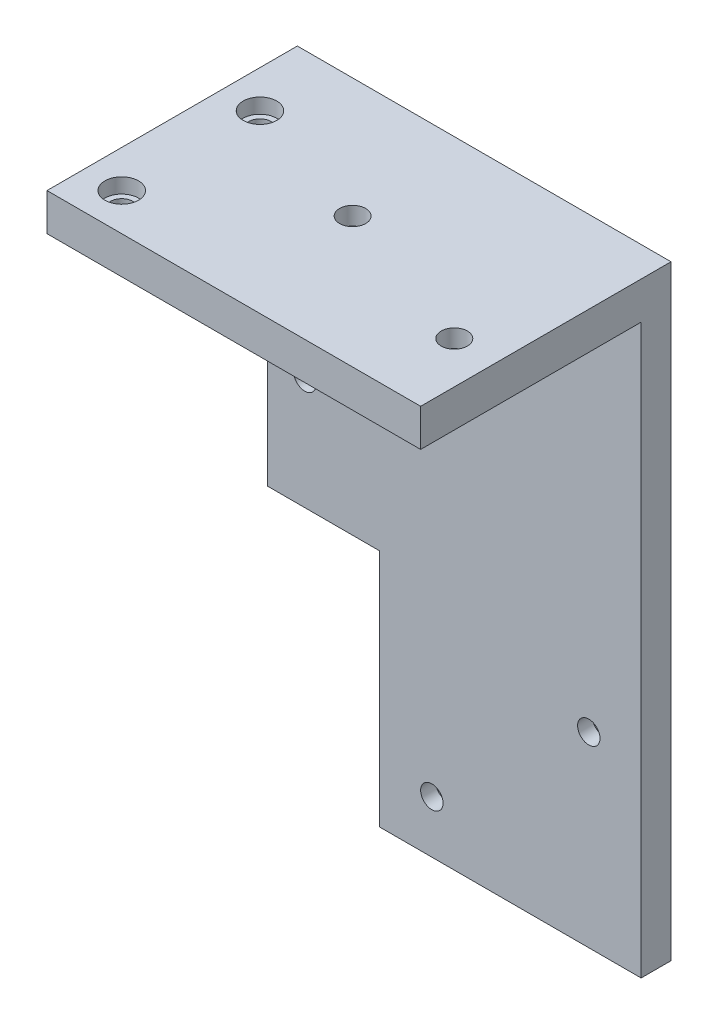
SolidWorks part; units mm, degrees
other "标注1"
sketch "草图3" plane through (0, 5, 29.5) normal (-0.6417, 0.7662, 0.0339) x (0.7661, 0.6384, 0.0747)
ref_plane "前视基准面" through (0, 0, 0) normal (0, 0, 1) x (1, 0, 0)
ref_plane "上视基准面" through (0, 0, 0) normal (0, 1, 0) x (1, 0, 0)
ref_plane "右视基准面" through (0, 0, 0) normal (1, 0, 0) x (0, 0, -1)
other "Configuration Table"
sketch "草图1" plane through (0, 0, 0) normal (0, 1, 0) x (1, 0, 0)
  line L33 (0, -29.5) -> (50, -29.5)
  line L34 (0, -29.5) -> (0, 0)
  line L35 (0, 0) -> (50, 0)
  line L36 (50, -29.5) -> (50, 0)
  line L37 (0, 0) -> (50, 0)
  line L38 (0, 0) -> (0, 4)
  line L39 (0, 4) -> (50, 4)
  line L44 (50, 0) -> (50, 4)
  line L45 (15, 4) -> (50, 4)
  line L46 (15, 4) -> (15, 0)
  line L47 (15, 0) -> (50, 0)
  line L48 (50, 4) -> (50, 0)
  circle A7 centre (23.4, -12) radius 1.75
  circle A8 centre (44.401, -19.4) radius 1.75
  circle A9 centre (23.4, -12) radius 3.1
  circle A10 centre (44.401, -19.4) radius 3.1
  point P0 (-90.6464, 22.0667)
  point P12 (24.1878, -12.7149)
  point P16 (0, 0)
  point P19 (0, 0)
  dimension "D1" = 3.5
  dimension "D2" = 29.5
  dimension "D3" = 6.2
  dimension "D4" = 50
  dimension "D5" = 4
  dimension "D6" = 35
extrude "凸台-拉伸1" add sketch "草图1" along normal blind 5 contours L34 | L36 L35 L34 L33 | A7 | A8
extrude "切除-拉伸1" cut sketch "草图1<17>" along normal blind 2.6 contours A9 | A10
sketch "草图1<17>" plane through (0, 0, 0) normal (0, 1, 0) x (1, 0, 0) same geometry as "草图1"
extrude "凸台-拉伸2" add sketch "草图1<18>" against normal blind 49 from surface contours L35 L44 L39 L38 | L46 L39 L38 L35 region at (7.5, 0, -2) region at (32.5, 0, -2) starting at face at (23.4, 5, 13.75)
sketch "草图1<18>" plane through (0, 0, 0) normal (0, 1, 0) x (1, 0, 0) same geometry as "草图1"
sketch "草图2" plane through (0, 5, 0) normal (0, 1, 0) x (1, 0, 0)
  line L0 (50, 4) -> (0, 4) construction
  line L1 (0, -29.5) -> (0, 4) construction
  line L2 (0, -29.5) -> (50, -29.5) construction
  circle A0 centre (5, -24.5) radius 2.25
  circle A1 centre (5, -24.5) radius 1.5
  circle A2 centre (5, -6) radius 2.25
  circle A3 centre (5, -6) radius 1.5
  dimension "D1" = 3
  dimension "D2" = 4.5
  dimension "D3" = 10
  dimension "D4" = 5
  dimension "D5" = 5
extrude "切除-拉伸2" cut sketch "草图2" against normal through all contours A3 | A1
extrude "切除-拉伸3" cut sketch "草图2<4>" against normal blind 2 contours A2 | A0
sketch "草图2<4>" plane through (0, 5, 0) normal (0, 1, 0) x (1, 0, 0) same geometry as "草图2"
sketch "草图4" plane through (0, 0, -4) normal (0, 0, -1) x (-1, 0, 0)
  line L0 (0, -44) -> (0, 5) construction
  line L1 (-50, -44) -> (0, -44) construction
  circle A0 centre (-5, -29) radius 2.25
  circle A1 centre (-5, -29) radius 1.5
  dimension "D1" = 4.5
  dimension "D2" = 3
  dimension "D3" = 5
  dimension "D4" = 15
extrude "切除-拉伸4" cut sketch "草图4" against normal through all contours A1
extrude "切除-拉伸5" cut sketch "草图4<3>" against normal blind 2 contours A0
sketch "草图4<3>" plane through (0, 0, -4) normal (0, 0, -1) x (-1, 0, 0) same geometry as "草图4"
sketch "草图5" plane through (0, -44, 0) normal (0, -1, 0) x (1, 0, 0)
  line L0 (50, 0) -> (0, 0) construction
  line L1 (50, -4) -> (15, -4)
  line L2 (50, -4) -> (50, 0)
  line L3 (50, 0) -> (15, 0)
  line L4 (15, -4) -> (15, 0)
  dimension "D1" = 35
extrude "凸台-拉伸4" add sketch "草图5" along normal blind 32
sketch "草图6" plane through (0, 0, -4) normal (0, 0, -1) x (-1, 0, 0)
  line L0 (-15, -76) -> (-15, -44) construction
  line L1 (-15, -76) -> (-50, -76) construction
  line L2 (-50, -76) -> (-50, 5) construction
  line L3 (-15, -44) -> (0, -44) construction
  circle A0 centre (-22, -69) radius 2.25
  circle A1 centre (-22, -69) radius 1.5
  circle A2 centre (-43, -51) radius 2.25
  circle A3 centre (-43, -51) radius 1.5
  dimension "D1" = 3
  dimension "D2" = 4.5
  dimension "D3" = 7
  dimension "D4" = 7
  dimension "D5" = 7
  dimension "D6" = 7
extrude "切除-拉伸6" cut sketch "草图6" against normal through all contours A3 | A1
extrude "切除-拉伸7" cut sketch "草图6<3>" against normal blind 2 contours A2 | A0
sketch "草图6<3>" plane through (0, 0, -4) normal (0, 0, -1) x (-1, 0, 0) same geometry as "草图6"
